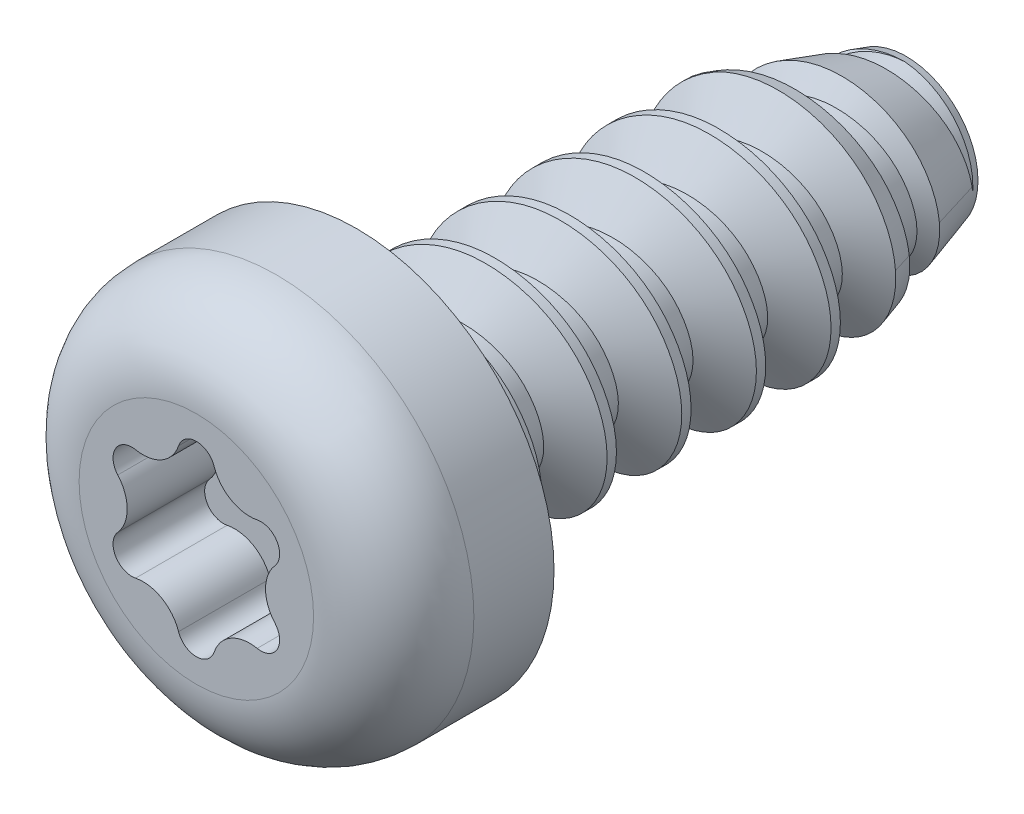
SolidWorks part; units mm, degrees
ref_plane "Front" through (0, 0, 0) normal (0, 0, 1) x (1, 0, 0)
ref_plane "Top" through (0, 0, 0) normal (0, 1, 0) x (1, 0, 0)
ref_plane "Right" through (0, 0, 0) normal (1, 0, 0) x (0, 0, -1)
sketch "HeadS" plane through (0, 0, 0) normal (0, 0, 1) x (1, 0, 0)
  circle A0 centre (0, 0) radius 4.31
extrude "Head" add sketch "HeadS" along normal blind 3.5
ref_plane "HeadTopRefP" through (0, 0, 3.5) normal (0, 0, 1) x (1, 0, 0)
sketch "HeadShapeS" plane through (0, 0, 0) normal (1, 0, 0) x (0, 0, -1)
  line L2 (-3.5, 4.31) -> (-3.5, -4.31) construction
  line L4 (0, 4.31) -> (-3.5, 4.31) construction
  line L5 (-1.75, 4.31) -> (-1.75, 4.41)
  line L6 (-1.75, 4.41) -> (-3.6, 4.41)
  line L7 (-3.6, 4.41) -> (-3.6, 2.56)
  line L8 (-3.6, 2.56) -> (-3.5, 2.56)
  line L11 (0, 0) -> (-3.5, 0) construction
  arc A0 (-3.5, 2.56) -> (-1.75, 4.31) centre (-1.75, 2.56) cw
  dimension "D1" = 0.1
  dimension "D2" = 0.1
revolve "HeadShape" cut sketch "HeadShapeS" angle 360 about L11
sketch "ThreadBodyS" plane through (0, 0, 0) normal (1, 0, 0) x (0, 0, -1)
  line L0 (0.4075, 1.6177) -> (0.9169, 2.5) construction
  line L2 (0.9169, 2.5) -> (1.1206, 2.5)
  line L3 (1.1206, 2.5) -> (1.63, 1.6177) construction
  line L4 (1.63, 1.6177) -> (0.4075, 1.6177) construction
  line L5 (1.63, 1.6177) -> (2.0375, 1.6177) construction
  line L6 (0.4075, 1.6177) -> (0, 1.6177) construction
  line L10 (0, 4.31) -> (0, -4.31) construction
  line L11 (0.9169, 2.5) -> (0.4075, 1.6177)
  line L12 (0.4075, 1.6177) -> (1.63, 1.6177)
  line L13 (1.63, 1.6177) -> (1.1206, 2.5)
  line L14 (0, 0) -> (-3.5, 0) construction
  line L15 (0, 0) -> (-3.5, 0) construction
  point P11 (1.0188, 2.5)
  dimension "D1" = 60
  dimension "D3" = 0.4075
  dimension "D4" = 0.2037
  dimension "Screw Dia" = 5
ref_plane "HeadBottomRefP" through (0, 0, -1.0188) normal (0, 0, 1) x (1, 0, 0)
sketch "ShaftS" plane through (0, 0, 0) normal (1, 0, 0) x (0, 0, -1)
  line L0 (0, 0) -> (12, 0)
  line L2 (12, -1.6177) -> (0, -1.6177) construction
  line L3 (12, 0) -> (12, 1.6177)
  line L4 (12, 1.6177) -> (0, 1.6177)
  line L5 (0, 0) -> (-3.5, 0) construction
  line L6 (0, 1.6177) -> (0, 0)
  line L7 (12, 0) -> (14.54, 0) construction
  line L8 (0.4075, 1.6177) -> (1.63, 1.6177) construction
  point P7 (0, 1.6177)
  dimension "D1" = 2.54
revolve "Shaft" add sketch "ShaftS" angle 360 about L7
sketch "ThreadProfileS" plane through (0, 0, -1.0188) normal (0, 0, 1) x (1, 0, 0)
  circle A0 centre (0, 0) radius 2.5
curve "ThreadProfile" pitch 1.63 height 2.445 radius 2.5 centre (0, 0, -1.0188) axis (0, 0, -1) start towards (0, 1, 0)
sweep "ThreadBody" add profiles "ThreadBodyS" path "ThreadProfile"
pattern_linear "TBLP" count 7 spacing 1.63 along (0, 0, -1) count 2 spacing 1.63 along (0, 0, 1) of "ThreadBody"
sketch "ThreadBottomCutS" plane through (0, 0, 0) normal (1, 0, 0) x (0, 0, -1)
  line L0 (12, 1.5677) -> (8.9691, 2.5)
  line L2 (8.9691, 2.5) -> (12, 2.5)
  line L3 (12, 2.5) -> (12, 1.5677) construction
  line L4 (12, 1.5677) -> (12, 0)
  line L5 (0, 0) -> (12, 0) construction
  line L6 (0.9169, 2.5) -> (1.1206, 2.5) construction
  line L7 (15.26, 0) -> (15.26, 2.5)
  line L8 (15.26, 2.5) -> (12, 2.5)
  line L9 (12, 0) -> (15.26, 0)
  dimension "D3" = 3.26
  dimension "D1" = 17.097
  dimension "D2" = 0.05
revolve "ThreadBottomCut" cut sketch "ThreadBottomCutS" angle 360 about L5
sketch "ScrewCutProfileS" plane through (0, 0, 3.5) normal (0, 0, 1) x (1, 0, 0)
  line L0 (0, 0) -> (0, 2.0365) construction
  line L1 (-0.7552, 1.3081) -> (0, 0)
  line L2 (0, 0) -> (0.7552, 1.3081)
  arc A0 (-0.7552, 1.3081) -> (-0.3882, 1.7571) centre (-1.1647, 2.0173) ccw
  arc A1 (-0.3882, 1.7571) -> (0.3882, 1.7571) centre (0, 1.627) cw
  arc A2 (0.3882, 1.7571) -> (0.7552, 1.3081) centre (1.1647, 2.0173) ccw
  circle A5 centre (0, 0) radius 2.0365 construction
  dimension "D2" = 0.4094
  dimension "D3" = 0.8189
  dimension "D1" = 60
ref_axis "ThreadAxis" through (0, 0, 3.5) along (0, 0, -1)
extrude "ScrewCutProfile" cut sketch "ScrewCutProfileS" against normal blind 2
pattern_circular "SCPCP" count 6 over 360 about axis through (0, 0, 3.5) along (0, 0, -1) of "ScrewCutProfile"
sketch "ThreadReferences" plane through (0, 0, 0) normal (1, 0, 0) x (0, 0, -1)
  line L0 (12, 2.5) -> (12, -2.5) construction
  point P0 (-3.5, 2.56)
  point P1 (0, 4.31)
  point P3 (8.9691, -2.5)
equation "\"D3@TBLP\"=\"Pitch@ThreadBodyS\""
equation "\"D1@TBLP\"=(\"Body Length@ShaftS\"/\"Pitch@ThreadBodyS\")"
equation "\"D1@ScrewCutProfile\"=\"Head Ht@Head\"*2/3.5"
equation "\"D3@ThreadBodyS\" = \"Pitch@ThreadBodyS\"/4"
equation "\"D4@ThreadBodyS\" = \"Pitch@ThreadBodyS\"/8"
equation "\"D4@TBLP\" = \"D3@TBLP\""
equation "\"D4@ThreadProfile\" = \"Pitch@ThreadBodyS\""
equation "\"D2@ScrewCutProfileS\" = \"Head Dia@HeadS\" * .0475"
equation "\"D3@ScrewCutProfileS\" = \"Head Dia@HeadS\" * .095"
equation "\"M@ScrewCutProfileS\" = \"Head Dia@HeadS\" * 0.4725"
equation "\"D3@ThreadBottomCutS\" = \"D4@ThreadProfile\" * 2"
